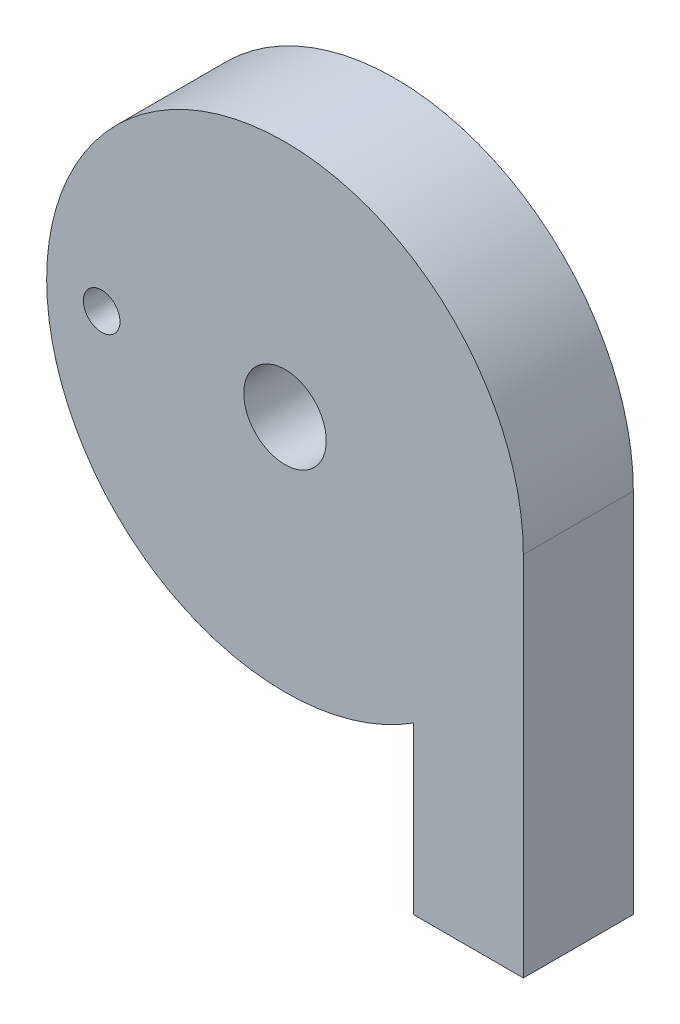
SolidWorks part; units mm, degrees
ref_plane "Front Plane" through (0, 0, 0) normal (0, 0, 1) x (1, 0, 0)
ref_plane "Top Plane" through (0, 0, 0) normal (0, 1, 0) x (1, 0, 0)
ref_plane "Right Plane" through (0, 0, 0) normal (1, 0, 0) x (0, 0, -1)
sketch "Sketch2" plane through (0, 0, 0) normal (0, 0, 1) x (1, 0, 0)
  line L0 (13, 0) -> (13, -20)
  line L1 (13, -20) -> (7, -20)
  line L2 (7, -20) -> (7, -10.9545)
  line L3 (10, 0) -> (10, -20) construction
  arc A0 (13, 0) -> (7, -10.9545) centre (0, 0) ccw
  circle A1 centre (0, 0) radius 10 construction
  dimension "D1" = 20
  dimension "D2" = 6
  dimension "D3" = 20
extrude "Boss-Extrude1" add sketch "Sketch2" along normal mid plane 6
hole_wizard "M4 Clearance Hole1" positions "Sketch3" profile "Sketch4" hole size "M4" standard "ANSI Metric" end condition up to next
sketch "Sketch3" plane through (0, 0, 3) normal (0, 0, 1) x (1, 0, 0)
  point P2 (0, 0)
sketch "Sketch4" plane through (0, 0, 3) normal (1, 0, 0) x (0, -1, 0)
  line L0 (0, 0) -> (0, 6)
  line L1 (0, 6) -> (2.25, 6)
  line L2 (2.25, 6) -> (2.25, 0)
  line L5 (2.25, 0) -> (0, 0)
  line L11 (0, -6.35) -> (0, 107.95) construction
  dimension "Thru Hole Dia." = 4.5
  dimension "Thru Hole Depth" = 6
sketch "Sketch5" plane through (0, -20, 0) normal (0, -1, 0) x (1, 0, 0)
  line L0 (13, 3) -> (7, -3) construction
  circle A0 centre (10, 0) radius 1.5875
  dimension "D1" = 3.175
extrude "Cut-Extrude1" cut sketch "Sketch5" against normal blind 20
sketch "Sketch7" plane through (0, 0, 3) normal (0, 0, 1) x (1, 0, 0)
  line L0 (-13, 0) -> (-10, 0) construction
  arc A0 (13, 0) -> (7, -10.9545) centre (0, 0) ccw construction
  circle A1 centre (-10, 0) radius 1
  point P8 (-11, 0)
  dimension "D1" = 2
  dimension "D2" = 2
extrude "Cut-Extrude2" cut sketch "Sketch7" against normal through all
ref_axis "Axis1" through (10, 0, 0) along (0, -1, 0)
